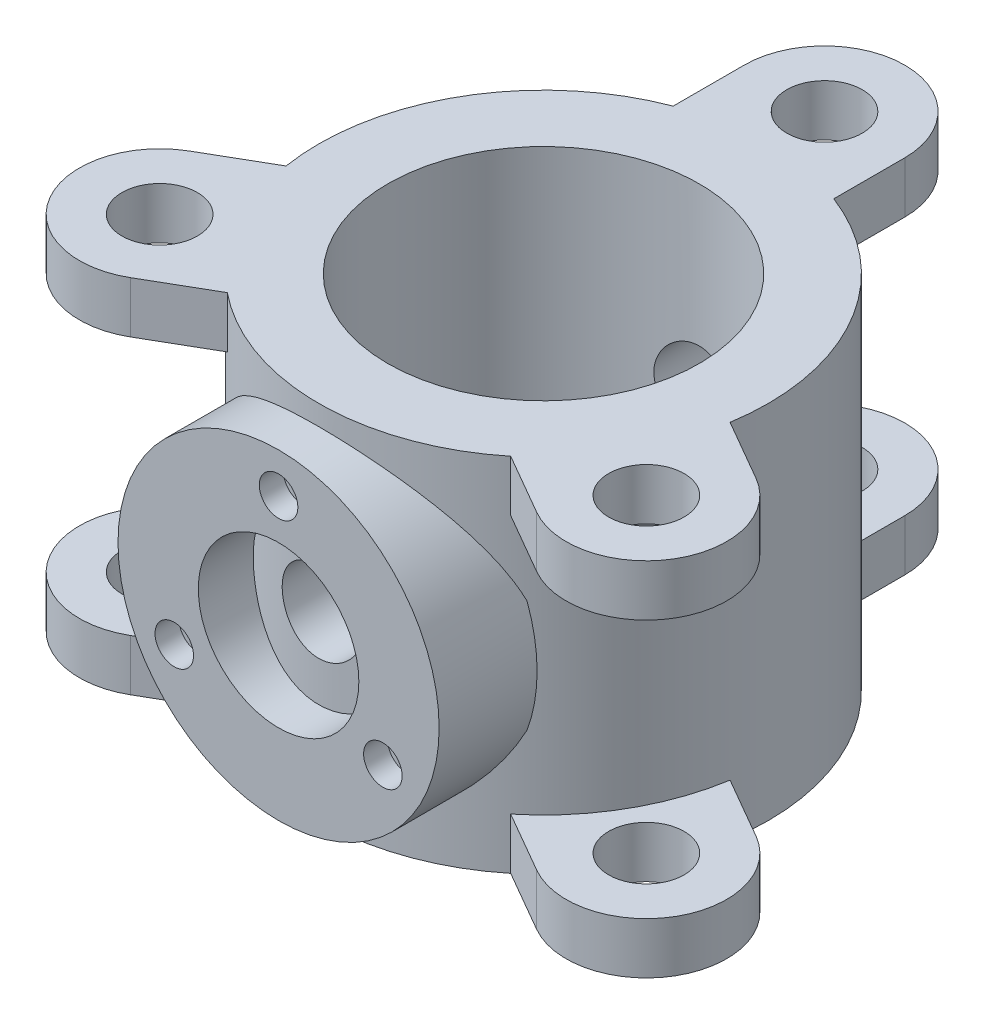
SolidWorks part; units mm, degrees
ref_plane "Front Plane" through (0, 0, 0) normal (0, 0, 1) x (1, 0, 0)
ref_plane "Top Plane" through (0, 0, 0) normal (0, 1, 0) x (1, 0, 0)
ref_plane "Right Plane" through (0, 0, 0) normal (1, 0, 0) x (0, 0, -1)
sketch "Sketch1" plane through (0, 0, 0) normal (0, 1, 0) x (1, 0, 0)
  line L0 (50, 175) -> (50, 130.767)
  line L1 (-50, 175) -> (-50, 130.767)
  line L2 (176.5544, -44.1987) -> (138.2475, -22.0822)
  line L3 (126.5544, -130.8013) -> (88.2475, -108.6848)
  line L4 (-126.5544, -130.8013) -> (-88.2475, -108.6848)
  line L5 (-176.5544, -44.1987) -> (-138.2475, -22.0822)
  circle A0 centre (0, 0) radius 97
  circle A1 centre (0, 0) radius 140
  circle A3 centre (0, 175) radius 23.5
  circle A4 centre (151.5544, -87.5) radius 23.5
  circle A5 centre (-151.5544, -87.5) radius 23.5
  arc A6 (50, 175) -> (-50, 175) centre (0, 175) ccw
  arc A7 (126.5544, -130.8013) -> (176.5544, -44.1987) centre (151.5544, -87.5) ccw
  arc A8 (-176.5544, -44.1987) -> (-126.5544, -130.8013) centre (-151.5544, -87.5) ccw
  point P13 (0, 0)
  point P31 (0, 0)
  dimension "D1" = 3
  dimension "D2" = 3
extrude "Boss-Extrude7" add sketch "Sketch1" along normal blind 225 contours A1 A0 region at (112.0637, 0, -77.1275)
extrude "Boss-Extrude9" add sketch "Sketch1<5>" along normal blind 32 contours L3 A7 L2 A1 A4 | L0 A6 L1 A1 A3 | L5 A8 L4 A1 A5 region at (48.626, 0, -152.8835) region at (156.5923, 0, 34.5412) region at (-122.6443, 0, 70.8087)
sketch "Sketch1<5>" plane through (0, 0, 0) normal (0, 1, 0) x (1, 0, 0) same geometry as "Sketch1"
ref_plane "Plane1" through (0, 112.5, 0) normal (0, 1, 0) x (1, 0, 0)
mirror "Mirror1" about plane through (0, 112.5, 0) normal (0, 1, 0) of "Boss-Extrude9"
ref_plane "Plane2" through (0, 0, 165) normal (0, 0, 1) x (1, 0, 0)
sketch "Sketch2" plane through (0, 0, 165) normal (0, 0, 1) x (1, 0, 0)
  line L0 (200.75, 112.5) -> (-200.75, 112.5) construction
  circle A0 centre (0, 112.5) radius 25
  circle A1 centre (0, 112.5) radius 50
  circle A2 centre (0, 112.5) radius 100
  circle A4 centre (0, 187.5) radius 12
  circle A5 centre (64.9519, 75) radius 12
  circle A6 centre (-64.9519, 75) radius 12
  point P6 (0, 0)
  point P16 (0, 112.5)
  dimension "D1" = 3
extrude "Boss-Extrude11" add sketch "Sketch2" against normal blind 61 contours A6 | A5 | A2 A6 A5 A4 A1 | A4 region at (-97.1716, 112.5, 165) region at (0, 187.5, 165) region at (64.9519, 75, 165) region at (-64.9519, 75, 165)
extrude "Cut-Extrude1" cut sketch "Sketch2<4>" against normal blind 15 contours A4 | A5 | A6 region at (0, 187.5, 165) region at (64.9519, 75, 165) region at (-64.9519, 75, 165)
sketch "Sketch2<4>" plane through (0, 0, 165) normal (0, 0, 1) x (1, 0, 0) same geometry as "Sketch2"
extrude "Cut-Extrude2" cut sketch "Sketch2<5>" against normal blind 547 contours A0 region at (0, 112.5, 165)
sketch "Sketch2<5>" plane through (0, 0, 165) normal (0, 0, 1) x (1, 0, 0) same geometry as "Sketch2"
